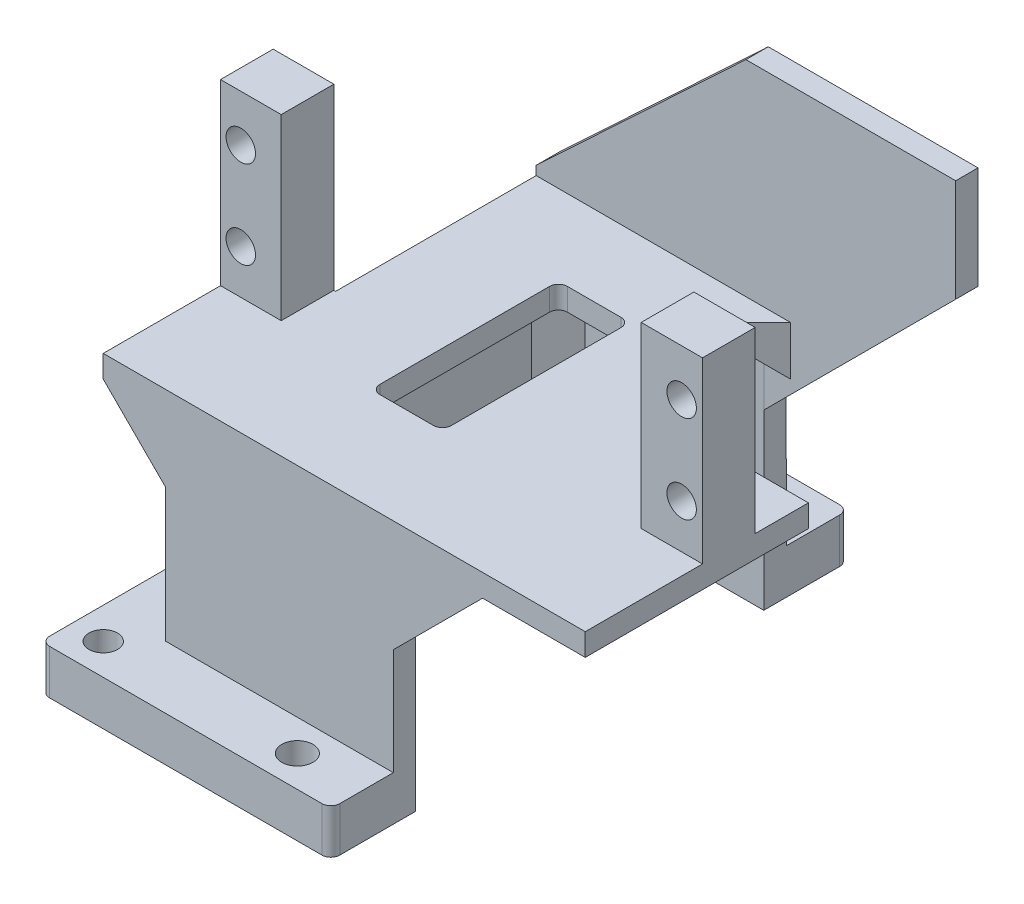
SolidWorks part; units mm, degrees
ref_plane "Front Plane" through (0, 0, 0) normal (0, 0, 1) x (1, 0, 0)
ref_plane "Top Plane" through (0, 0, 0) normal (0, 1, 0) x (1, 0, 0)
ref_plane "Right Plane" through (0, 0, 0) normal (1, 0, 0) x (0, 0, -1)
sketch "Sketch1" plane through (0, 0, 0) normal (0, 1, 0) x (1, 0, 0)
  line L0 (0, 40) -> (23, 40)
  line L1 (30, 0) -> (80, 0)
  line L2 (0, 20) -> (0, 40)
  line L3 (0, 100) -> (110, 100)
  line L4 (110, 20) -> (110, 40)
  line L5 (23, 40) -> (23, 79)
  line L6 (23, 79) -> (0, 79)
  line L7 (110, 79) -> (87, 79)
  line L8 (87, 79) -> (87, 40)
  line L9 (87, 40) -> (110, 40)
  line L10 (0, 79) -> (0, 100)
  line L11 (110, 79) -> (110, 100)
  line L12 (0, 20) -> (30, 0)
  line L13 (110, 20) -> (80, 0)
  point P0 (55, 0)
  dimension "D1" = 100
  dimension "D2" = 110
  dimension "23" = 23
  dimension "D4" = 40
  dimension "20" = 23
  dimension "D5" = 39
  dimension "40" = 40
extrude "Boss-Extrude1" add sketch "Sketch1" along normal blind 3.5
sketch "Sketch2" plane through (0, 3.5, 0) normal (0, 1, 0) x (1, 0, 0)
  line L0 (0, 79) -> (23, 79)
  line L1 (23, 79) -> (23, 40)
  line L2 (23, 40) -> (0, 40)
  line L3 (0, 40) -> (0, 37.5)
  line L4 (0, 40) -> (0, 20) construction
  line L5 (0, 37.5) -> (25.5, 37.5)
  line L6 (25.5, 37.5) -> (25.5, 81.5)
  line L7 (25.5, 81.5) -> (0, 81.5)
  line L8 (0, 100) -> (0, 79) construction
  line L9 (0, 81.5) -> (0, 79)
  line L10 (110, 81.5) -> (84.5, 81.5)
  line L11 (110, 79) -> (110, 100) construction
  line L12 (84.5, 81.5) -> (84.5, 37.5)
  line L13 (84.5, 37.5) -> (110, 37.5)
  line L14 (110, 20) -> (110, 40) construction
  line L15 (110, 37.5) -> (110, 40)
  line L16 (110, 40) -> (87, 40)
  line L17 (87, 40) -> (87, 79)
  line L18 (110, 81.5) -> (110, 79)
  line L19 (110, 79) -> (87, 79)
  dimension "D1" = 2.5
  dimension "3" = 2.5
  dimension "D2" = 2.5
  dimension "D3" = 2.5
  dimension "D4" = 2.5
  dimension "D5" = 2.5
extrude "Boss-Extrude2" add sketch "Sketch2" along normal blind 21
sketch "Sketch3" plane through (0, 24.5, 0) normal (0, 1, 0) x (1, 0, 0)
  line L1 (23, 79) -> (0, 79)
  line L2 (23, 79) -> (23, 40)
  line L3 (23, 40) -> (0, 40)
  line L4 (0, 79) -> (0, 40)
  line L5 (87, 79) -> (110, 79)
  line L6 (87, 79) -> (87, 40)
  line L7 (87, 40) -> (110, 40)
  line L8 (110, 79) -> (110, 40)
extrude "Boss-Extrude3" add sketch "Sketch3" against normal blind 2.5
sketch "Sketch5" plane through (0, 24.5, 0) normal (0, 1, 0) x (1, 0, 0)
  line L0 (55, 100) -> (55, 0) construction
  line L1 (110, 100) -> (0, 100) construction
  line L2 (30, 0) -> (80, 0) construction
  line L3 (110, 62.5) -> (131.5, 62.5)
  line L4 (0, 37.5) -> (-21.5, 37.5)
  line L5 (0, 37.5) -> (0, 62.5)
  line L6 (0, 62.5) -> (-21.5, 62.5)
  line L7 (-21.5, 37.5) -> (-21.5, 62.5)
  line L8 (131.5, 37.5) -> (131.5, 62.5)
  line L9 (110, 37.5) -> (131.5, 37.5)
  line L10 (110, 37.5) -> (110, 62.5)
  line L13 (25.5, 56.54) -> (25.5, 37.5)
  line L14 (25.5, 37.5) -> (32.57, 37.5)
  line L15 (32.57, 56.54) -> (32.57, 37.5)
  line L18 (84.5, 56.54) -> (84.5, 37.5)
  line L19 (84.5, 37.5) -> (77.43, 37.5)
  line L20 (77.43, 56.54) -> (77.43, 37.5)
  line L21 (25.5, 37.5) -> (25.5, 56.54) construction
  line L23 (25.5, 56.54) -> (32.57, 56.54)
  line L24 (77.43, 56.54) -> (84.5, 56.54) construction
  line L25 (84.5, 56.54) -> (77.43, 56.54)
  dimension "D1" = 21.5
  dimension "D2" = 25
extrude "Boss-Extrude5" add sketch "Sketch5" against normal blind 2.5
sketch "Sketch6" plane through (0, 24.5, 0) normal (0, 1, 0) x (1, 0, 0)
  line L0 (55, 100) -> (55, 0) construction
  line L1 (110, 100) -> (0, 100) construction
  line L2 (30, 0) -> (80, 0) construction
  line L3 (32.57, 37.5) -> (32.57, 56.54) construction
  line L4 (25.5, 56.54) -> (32.57, 56.54)
  line L5 (25.5, 56.54) -> (25.5, 50.64)
  line L6 (25.5, 50.64) -> (32.57, 50.64)
  line L7 (32.57, 56.54) -> (32.57, 50.64)
  line L8 (84.5, 50.64) -> (77.43, 50.64)
  line L9 (77.43, 56.54) -> (77.43, 50.64)
  line L10 (84.5, 56.54) -> (77.43, 56.54)
  line L11 (84.5, 56.54) -> (84.5, 50.64)
  line L12 (-21.5, 62.5) -> (-21.5, 37.5) construction
  line L13 (-21.5, 56.54) -> (-14.43, 56.54)
  line L14 (-21.5, 56.54) -> (-21.5, 50.64)
  line L15 (-21.5, 50.64) -> (-14.43, 50.64)
  line L16 (-14.43, 56.54) -> (-14.43, 50.64)
  line L17 (131.5, 50.64) -> (124.43, 50.64)
  line L18 (124.43, 56.54) -> (124.43, 50.64)
  line L19 (131.5, 56.54) -> (124.43, 56.54)
  line L20 (131.5, 56.54) -> (131.5, 50.64)
  dimension "D1" = 5.9
  dimension "D2" = 7.07
  dimension "D3" = 7.07
extrude "Boss-Extrude6" add sketch "Sketch6" along normal blind 20
sketch "Sketch7" plane through (0, 24.5, 0) normal (0, 1, 0) x (1, 0, 0)
  line L0 (55, 100) -> (55, 0) construction
  line L1 (110, 100) -> (0, 100) construction
  line L2 (30, 0) -> (80, 0) construction
  line L3 (25.5, 56.54) -> (25.5, 81.5) construction
  line L4 (0, 81.5) -> (25.5, 81.5)
  line L6 (0, 79) -> (25.5, 79)
  line L7 (25.5, 81.5) -> (25.5, 79)
  line L8 (110, 79) -> (84.5, 79)
  line L9 (84.5, 81.5) -> (84.5, 79)
  line L10 (110, 81.5) -> (84.5, 81.5)
  line L13 (0, 79) -> (-21.5, 79)
  line L15 (0, 81.5) -> (-21.5, 81.5)
  line L16 (-21.5, 79) -> (-21.5, 81.5)
  line L18 (110, 79) -> (131.5, 79)
  line L20 (110, 81.5) -> (131.5, 81.5)
  line L21 (131.5, 79) -> (131.5, 81.5)
  dimension "D1" = 2.5
extrude "Boss-Extrude7" add sketch "Sketch7" along normal blind 23
fillet "Fillet1" radius 10 4 edges at (0, 22, -38.75) (110, 22, -38.75) (0, 24.5, -80.25) (110, 24.5, -80.25) profile chamfer
sketch "Sketch9" plane through (0, 0, -81.5) normal (0, 0, -1) x (-1, 0, 0)
  line L0 (-131.5, 47.5) -> (-84.5, 47.5) construction
  line L3 (-131.5, 47.5) -> (-131.5, 24.5) construction
  line L4 (-55, 0) -> (-55, 48.0721) construction
  line L5 (-110, 0) -> (0, 0) construction
  circle A0 centre (-114.55, 34.35) radius 2.475
  circle A1 centre (4.55, 34.35) radius 2.475
  point P6 (-114.55, 34.35)
  dimension "D2" = 4.95
  dimension "D1" = 13.15
  dimension "D3" = 16.95
extrude "Boss-Extrude8" add sketch "Sketch9" along normal blind 9
fillet "Fillet2" radius 0.5 2 edges at (-2.075, 34.35, -90.5) (112.075, 34.35, -90.5)
sketch "Sketch10" plane through (0, 0, -50.64) normal (0, 0, 1) x (1, 0, 0)
  line L0 (55, 0) -> (55, 49.7444) construction
  line L1 (30, 0) -> (80, 0) construction
  line L2 (129.16, 44.5) -> (129.16, 24.5) construction
  line L3 (124.43, 44.5) -> (131.5, 44.5) construction
  line L4 (124.43, 24.5) -> (131.5, 24.5) construction
  line L5 (131.5, 44.5) -> (131.5, 24.5) construction
  line L6 (79.77, 44.5) -> (79.77, 24.5) construction
  line L7 (77.43, 44.5) -> (84.5, 44.5) construction
  line L8 (77.43, 24.5) -> (84.5, 24.5) construction
  line L9 (77.43, 44.5) -> (77.43, 24.5) construction
  circle A0 centre (129.16, 39.27) radius 1.65
  circle A1 centre (129.16, 29.43) radius 1.65
  circle A2 centre (79.77, 39.27) radius 1.65
  circle A3 centre (79.77, 29.43) radius 1.65
  circle A4 centre (-19.16, 29.43) radius 1.65
  circle A5 centre (-19.16, 39.27) radius 1.65
  circle A6 centre (30.23, 39.27) radius 1.65
  circle A7 centre (30.23, 29.43) radius 1.65
  dimension "D3" = 5.23
  dimension "D4" = 3.3
  dimension "D5" = 4.93
  dimension "D6" = 3.3
  dimension "D7" = 3.3
  dimension "D8" = 3.3
  dimension "D1" = 2.34
  dimension "D2" = 2.34
extrude "Cut-Extrude1" cut sketch "Sketch10" against normal blind 9
sketch "Sketch11" plane through (0, 0, -50.64) normal (0, 0, 1) x (1, 0, 0)
  line L0 (-21.5, 24.5) -> (-14.43, 24.5) construction
  line L1 (-14.43, 44.5) -> (-14.63, 44.5)
  line L2 (-14.43, 44.5) -> (-14.43, 24.5)
  line L3 (-14.43, 24.5) -> (-14.63, 24.5)
  line L4 (-14.63, 44.5) -> (-14.63, 24.5)
  line L5 (25.5, 24.5) -> (32.57, 24.5) construction
  line L6 (25.5, 44.5) -> (25.7, 44.5)
  line L7 (25.5, 44.5) -> (25.5, 24.5)
  line L8 (25.5, 24.5) -> (25.7, 24.5)
  line L9 (25.7, 44.5) -> (25.7, 24.5)
  line L10 (55, 3.5) -> (55, 47.4628) construction
  line L11 (30, 3.5) -> (80, 3.5) construction
  line L12 (84.5, 24.5) -> (84.3, 24.5)
  line L13 (84.3, 44.5) -> (84.3, 24.5)
  line L14 (84.5, 44.5) -> (84.3, 44.5)
  line L15 (84.5, 44.5) -> (84.5, 24.5)
  line L16 (124.43, 24.5) -> (124.63, 24.5)
  line L17 (124.63, 44.5) -> (124.63, 24.5)
  line L18 (124.43, 44.5) -> (124.63, 44.5)
  line L19 (124.43, 44.5) -> (124.43, 24.5)
  dimension "D1" = 0.2
  dimension "D2" = 0.2
extrude "Cut-Extrude2" cut sketch "Sketch11" against normal blind 9
sketch "Sketch12" plane through (0, 0, -81.5) normal (0, 0, -1) x (-1, 0, 0)
  line L0 (-108, 47.5) -> (-84.5, 25.5)
  line L1 (-131.5, 47.5) -> (-84.5, 47.5) construction
  line L2 (-84.5, 47.5) -> (-84.5, 3.5) construction
  line L3 (-84.5, 25.5) -> (-84.5, 47.5)
  line L4 (-84.5, 47.5) -> (-108, 47.5)
  line L5 (-55, 3.5) -> (-55, 47.5) construction
  line L6 (-110, 3.5) -> (0, 3.5) construction
  line L7 (-25.5, 25.5) -> (-25.5, 47.5)
  line L8 (-2, 47.5) -> (-25.5, 25.5)
  line L9 (-25.5, 47.5) -> (-2, 47.5)
  line L10 (-120, 24.5) -> (-131.5, 36)
  line L11 (-131.5, 47.5) -> (-131.5, 24.5) construction
  line L12 (-131.5, 36) -> (-131.5, 24.5)
  line L13 (-131.5, 24.5) -> (-120, 24.5)
  line L14 (10, 24.5) -> (21.5, 36)
  line L15 (21.5, 47.5) -> (21.5, 24.5) construction
  line L16 (21.5, 36) -> (21.5, 24.5)
  line L17 (21.5, 24.5) -> (10, 24.5)
extrude "Cut-Extrude3" cut sketch "Sketch12" against normal blind 9
fillet "Fillet3" radius 3 2 edges at (110, 23.25, -62.5) (0, 23.25, -62.5) profile chamfer
sketch "Sketch13" plane through (0, 3.5, 0) normal (0, 1, 0) x (1, 0, 0)
  line L0 (55, 100) -> (55, 0) construction
  line L1 (110, 100) -> (0, 100) construction
  line L2 (30, 0) -> (80, 0) construction
  line L3 (0, 30.5) -> (32.5, 30.5)
  line L4 (0, 37.5) -> (0, 20) construction
  line L5 (32.5, 30.5) -> (32.5, 88.5)
  line L6 (32.5, 88.5) -> (0, 88.5)
  line L7 (0, 100) -> (0, 81.5) construction
  line L8 (0, 88.5) -> (0, 81.5)
  line L9 (0, 81.5) -> (25.5, 81.5)
  line L10 (25.5, 81.5) -> (25.5, 37.5)
  line L11 (25.5, 37.5) -> (0, 37.5)
  line L12 (0, 37.5) -> (0, 30.5)
  line L13 (84.5, 37.5) -> (110, 37.5)
  line L14 (84.5, 81.5) -> (84.5, 37.5)
  line L15 (110, 81.5) -> (84.5, 81.5)
  line L16 (110, 88.5) -> (110, 81.5)
  line L17 (77.5, 88.5) -> (110, 88.5)
  line L18 (77.5, 30.5) -> (77.5, 88.5)
  line L19 (110, 30.5) -> (77.5, 30.5)
  line L20 (110, 37.5) -> (110, 30.5)
  dimension "D1" = 7
  dimension "D2" = 7
  dimension "D3" = 7
extrude "Boss-Extrude9" add sketch "Sketch13" along normal blind 5
sketch "Sketch14" plane through (0, 8.5, 0) normal (0, 1, 0) x (1, 0, 0)
  line L0 (55, 100) -> (55, 0) construction
  line L1 (110, 100) -> (0, 100) construction
  line L2 (30, 0) -> (80, 0) construction
  line L3 (0, 85) -> (29, 85) construction
  line L4 (0, 88.5) -> (0, 81.5) construction
  line L5 (29, 85) -> (29, 34) construction
  line L6 (29, 34) -> (0, 34) construction
  line L7 (0, 37.5) -> (0, 30.5) construction
  line L8 (32.5, 30.5) -> (32.5, 88.5) construction
  circle A0 centre (7.25, 34) radius 1.7478
  circle A3 centre (7.25, 85) radius 1.6
  circle A5 centre (29, 34) radius 1.6
  circle A6 centre (29, 59.5) radius 1.6
  circle A7 centre (29, 85) radius 1.6
  circle A8 centre (81, 34) radius 1.6
  circle A9 centre (102.75, 34) radius 1.7478
  circle A10 centre (81, 59.5) radius 1.6
  circle A11 centre (81, 85) radius 1.6
  circle A12 centre (102.75, 85) radius 1.6
  dimension "D2" = 3.2
  dimension "D3" = 7.25
  dimension "D4" = 3.2
  dimension "D6" = 3.2
  dimension "D7" = 7.25
  dimension "3.2" = 3.2
  dimension "D1" = 3.5
extrude "Cut-Extrude4" cut sketch "Sketch14" against normal blind 15
sketch "Sketch15" plane through (0, 0, -100) normal (0, 0, -1) x (-1, 0, 0)
  line L1 (-110, 3.5) -> (0, 3.5)
  line L2 (-110, 3.5) -> (-110, 0)
  line L3 (-110, 0) -> (0, 0)
  line L4 (0, 3.5) -> (0, 0)
  line L5 (21.5, 47.5) -> (-77.5, 47.5)
  line L6 (21.5, 47.5) -> (21.5, 3.5)
  line L7 (21.5, 3.5) -> (-77.5, 3.5)
  line L8 (-77.5, 47.5) -> (-77.5, 3.5)
  line M3 (0, 3.5) -> (-110, 3.5)
extrude "Cut-Extrude5" cut sketch "Sketch15" against normal blind 150 contours L5 L8 L7 L6 M3 | L3 L4 L1 L2 region at (28, 25.5, -100)
fillet "Fillet4" radius 7 1 edges at (84.5, 22, -47.02) profile chamfer
fillet "Fillet5" radius 3 3 edges at (98.5, 22, -79) (103.5, 22, -40) (87, 22, -59.5) profile chamfer
fillet "Fillet6" radius 3 1 edges at (110, 21.75, -79) profile chamfer
sketch "Sketch17" plane through (0, 22, 0) normal (0, -1, 0) x (1, 0, 0)
  line L0 (90, -43) -> (90, -76) construction
  line L1 (96, -49) -> (104, -49)
  line L2 (96, -49) -> (96, -70)
  line L3 (96, -70) -> (104, -70)
  line L4 (104, -49) -> (104, -70)
  line L5 (120, -43) -> (90, -43) construction
  line L6 (110, -65.5) -> (110, -76) construction
  line L7 (90, -76) -> (110, -76) construction
  dimension "D1" = 6
  dimension "D2" = 6
  dimension "D3" = 6
  dimension "D4" = 6
extrude "Cut-Extrude6" cut sketch "Sketch17" against normal blind 150
fillet "Fillet7" radius 1 4 edges at (104, 23.25, -70) (104, 23.25, -49) (96, 23.25, -49) (96, 23.25, -70)
fillet "Fillet9" radius 3 2 edges at (87, 11.25, -79) (87, 11.25, -40) profile chamfer
sketch "Sketch19" plane through (0, 3.5, 0) normal (0, -1, 0) x (1, 0, 0)
  line L0 (110, -40) -> (110, -30.5)
  line L1 (110, -30.5) -> (77.5, -30.5)
  line L2 (77.5, -30.5) -> (77.5, -88.5)
  line L3 (77.5, -88.5) -> (110, -88.5)
  line L4 (110, -88.5) -> (110, -79)
  line L5 (110, -79) -> (90, -79)
  line L6 (90, -79) -> (87, -76)
  line L7 (87, -76) -> (87, -43)
  line L8 (87, -43) -> (90, -40)
  line L9 (90, -40) -> (110, -40)
  circle A0 centre (102.75, -34) radius 1.7478
  circle A1 centre (81, -34) radius 1.6
  circle A2 centre (81, -59.5) radius 1.6
  circle A3 centre (81, -85) radius 1.6
  circle A4 centre (102.75, -85) radius 1.6
extrude "Boss-Extrude10" add sketch "Sketch19" along normal blind 8.43
sketch "Sketch20" plane through (0, 8.5, 0) normal (0, 1, 0) x (1, 0, 0)
  line L1 (77.5, 88.5) -> (77.5, 30.5) construction
  line L2 (110, 88.5) -> (77.5, 88.5)
  line L3 (110, 88.5) -> (110, 81.5494)
  line L4 (110, 81.5494) -> (84.5, 81.5494)
  line L5 (77.5, 88.5) -> (77.5, 81.5494)
  line L6 (77.5, 30.5) -> (110, 30.5) construction
  line L8 (77.5, 81.5494) -> (77.5, 30.5)
  line L9 (77.5, 30.5) -> (84.5, 30.5)
  line L10 (84.5, 81.5494) -> (84.5, 37.5)
  line L12 (84.5, 30.5) -> (110, 30.5)
  line L14 (84.5, 37.5) -> (110, 37.5)
  line L15 (110, 30.5) -> (110, 37.5)
extrude "Cut-Extrude7" cut sketch "Sketch20" against normal blind 8.43
fillet "Fillet10" radius 1 4 edges at (77.5, -2.43, -88.5) (110, -2.43, -88.5) (77.5, -2.43, -30.5) (110, -2.43, -30.5)
